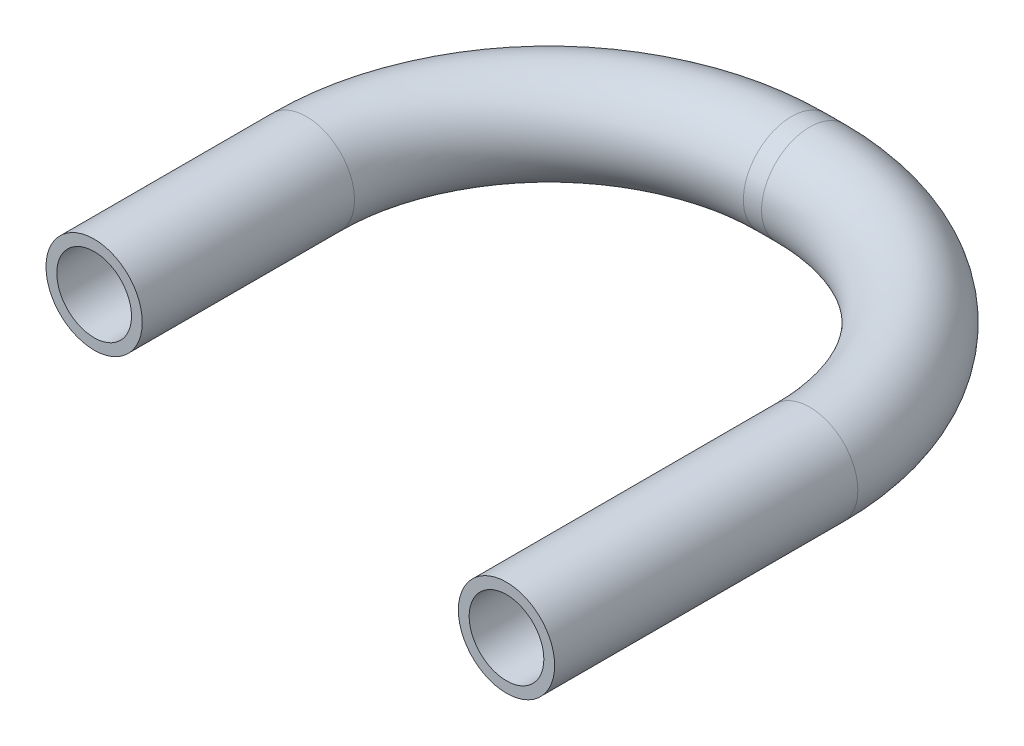
SolidWorks part; units mm, degrees
ref_plane "Front Plane" through (0, 0, 0) normal (0, 0, 1) x (1, 0, 0)
ref_plane "Top Plane" through (0, 0, 0) normal (0, 1, 0) x (1, 0, 0)
ref_plane "Right Plane" through (0, 0, 0) normal (1, 0, 0) x (0, 0, -1)
sketch "Sketch1" plane through (0, 0, 0) normal (0, 1, 0) x (1, 0, 0)
  line L0 (0, 0) -> (0, 14)
  line L1 (16, 30) -> (17.2, 30)
  line L2 (33.2, 14) -> (33.2, -6)
  arc A0 (17.2, 30) -> (33.2, 14) centre (17.2, 14) cw
  arc A1 (0, 14) -> (16, 30) centre (16, 14) cw
  dimension "D1" = 16
  dimension "D2" = 16
  dimension "D3" = 14
  dimension "D4" = 20
  dimension "D5" = 33.2
sketch "Sketch2" plane through (0, 0, 0) normal (0, 0, 1) x (1, 0, 0)
  circle A0 centre (0, 0) radius 3.175
  dimension "D1" = 6.35
sweep "Sweep-Thin1" add profiles "Sketch2" path "Sketch1" parameters "D1"=0.7112
